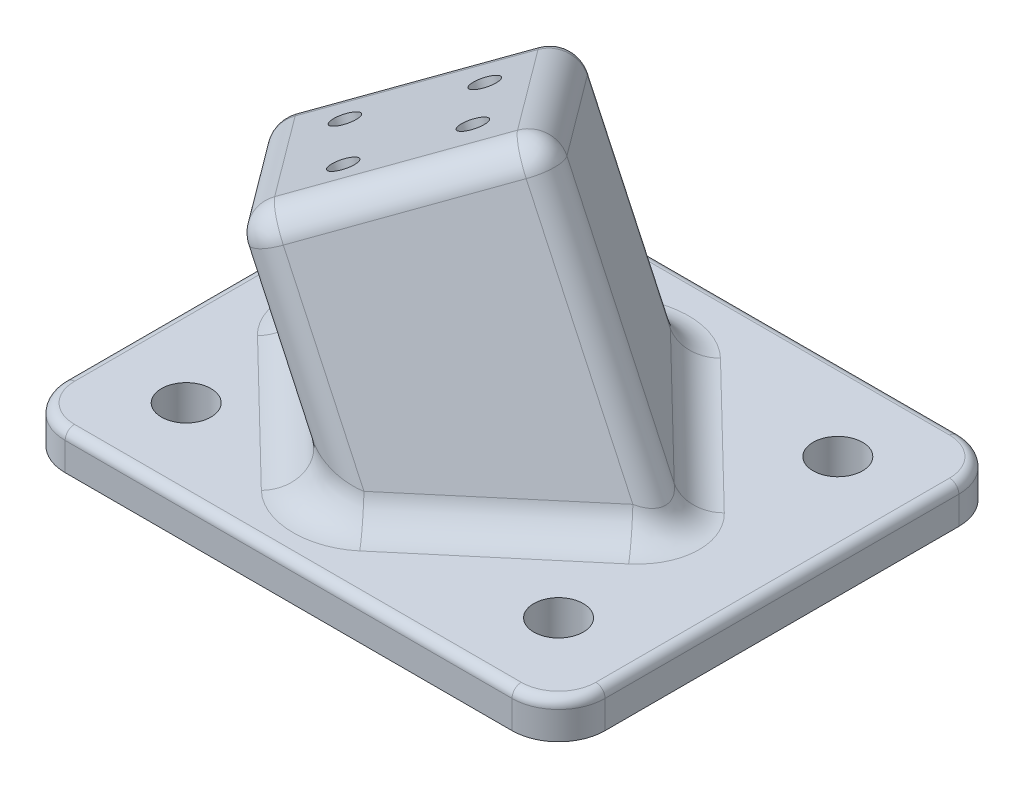
SolidWorks part; units mm, degrees
ref_plane "Front Plane" through (0, 0, 0) normal (0, 0, 1) x (1, 0, 0)
ref_plane "Top Plane" through (0, 0, 0) normal (0, 1, 0) x (1, 0, 0)
ref_plane "Right Plane" through (0, 0, 0) normal (1, 0, 0) x (0, 0, -1)
sketch "Sketch1" plane through (0, 0, 0) normal (0, 1, 0) x (1, 0, 0)
  line L1 (0, 0) -> (63.5, 0)
  line L2 (0, 0) -> (0, -50.8)
  line L3 (0, -50.8) -> (63.5, -50.8)
  line L4 (63.5, 0) -> (63.5, -50.8)
  dimension "D1" = 63.5
  dimension "D2" = 50.8
extrude "Boss-Extrude1" add sketch "Sketch1" along normal blind 5.08
sketch "Sketch2" plane through (0, 5.08, 0) normal (0, 1, 0) x (1, 0, 0)
  line L1 (0, 0) -> (0, -50.8) construction
  line L2 (63.5, 0) -> (0, 0) construction
  point P0 (6.35, -6.35)
  point P1 (57.15, -6.35)
  point P2 (57.15, -44.45)
  point P3 (6.35, -44.45)
  dimension "D1" = 50.8
  dimension "D2" = 38.1
  dimension "D3" = 50.8
  dimension "D4" = 38.1
  dimension "D5" = 6.35
  dimension "D6" = 6.35
ref_plane "Plane2" through (11.3415, -24.3219, 0) normal (-0.4226, 0.9063, 0) x (0, 0, -1)
sketch "Sketch5" plane through (0, 0, 0) normal (0, -1, 0) x (1, 0, 0)
  line L0 (0, 0) -> (0, 50.8) construction
  line L1 (0, 50.8) -> (63.5, 50.8)
  line L2 (0, 50.8) -> (0, 0)
  line L3 (0, 0) -> (63.5, 0)
  line L4 (63.5, 50.8) -> (63.5, 0)
  line L5 (63.5, 0) -> (0, 0) construction
  dimension "D1" = 50.8
  dimension "D2" = 63.5
  dimension "D3" = 0
  dimension "D4" = 0
hole_wizard "1/4 Clearance Hole1" positions "3DSketch2" profile "Sketch8" hole size "1/4" standard "ANSI Inch" end condition up to next
sketch3d "3DSketch2"
  point P0 (6.35, 5.08, 6.35)
  point P3 (6.35, 5.08, 44.45)
  point P6 (57.15, 5.08, 44.45)
  point P9 (57.15, 5.08, 6.35)
sketch "Sketch8" plane through (6.35, 5.08, 6.35) normal (1, 0, 0) x (0, 0, 1)
  line L0 (0, 0) -> (0, 5.08)
  line L1 (0, 5.08) -> (3.3782, 5.08)
  line L2 (3.3782, 5.08) -> (3.3782, 0)
  line L5 (3.3782, 0) -> (0, 0)
  line L11 (0, -6.35) -> (0, 107.95) construction
  dimension "Thru Hole Dia." = 6.7564
  dimension "Thru Hole Depth" = 5.08
sketch "Sketch13" plane through (0, 5.08, 0) normal (0, 1, 0) x (1, 0, 0)
  line L0 (0, 0) -> (63.5, 0)
  line L1 (63.5, 0) -> (63.5, -50.8)
  line L2 (63.5, -50.8) -> (0, -50.8)
  line L3 (0, 0) -> (0, -50.8) construction
  line L4 (0, -50.8) -> (63.5, -50.8) construction
  line L5 (0, -50.8) -> (0, 0)
  line L6 (-5.08, 5.08) -> (68.58, 5.08)
  line L7 (68.58, 5.08) -> (68.58, -55.88)
  line L8 (68.58, -55.88) -> (-5.08, -55.88)
  line L9 (-5.08, -55.88) -> (-5.08, 5.08)
  dimension "D1" = 73.66
  dimension "D2" = 60.96
  dimension "D3" = 5.08
  dimension "D4" = 5.08
extrude "Boss-Extrude3" add sketch "Sketch13" against normal blind 5.08
fillet "Fillet4" radius 1.27 4 edges at (68.58, 5.08, 25.4) (31.75, 5.08, -5.08) (31.75, 5.08, 55.88) (-5.08, 5.08, 25.4)
sketch "Sketch14" plane through (11.3415, -24.3219, 0) normal (-0.4226, 0.9063, 0) x (0, 0, -1)
  line L0 (-25.4, -8.3855) -> (-48.992, -30.3854)
  line L1 (-48.992, -30.3854) -> (-26.9921, -53.9775)
  line L2 (-26.9921, -53.9775) -> (-3.4001, -31.9775)
  line L3 (-3.4001, -31.9775) -> (-25.4, -8.3855)
  line L4 (5.08, 4.604) -> (-55.88, 4.604) construction
  line L6 (-55.88, -63.7648) -> (-55.88, 2.9939) construction
  point P6 (-25.4, 4.604)
  point P11 (-55.88, -30.3854)
  dimension "D1" = 90
  dimension "D2" = 90
  dimension "D3" = 32.258
  dimension "D4" = 32.258
extrude "Boss-Extrude4" add sketch "Sketch14" along normal blind 50.8
sketch "Sketch16" plane through (0, 0, 0) normal (0, -1, 0) x (1, 0, 0)
  line L1 (0, 50.8) -> (63.5, 50.8)
  line L2 (0, 50.8) -> (0, 0)
  line L3 (0, 0) -> (63.5, 0)
  line L4 (63.5, 50.8) -> (63.5, 0)
sketch "Sketch17" plane through (11.3415, -24.3219, 0) normal (0.4226, -0.9063, 0) x (0.9063, 0.4226, 0)
  line L0 (11.9755, 25.5254) -> (31.8522, 6.99)
  line L1 (31.8522, 6.99) -> (50.3875, 26.8667)
  line L2 (50.3875, 26.8667) -> (30.5108, 45.4021)
  line L3 (30.5108, 45.4021) -> (11.9755, 25.5254)
  line L5 (31.9775, 3.4001) -> (8.3855, 25.4) construction
  line L6 (8.3855, 25.4) -> (30.3854, 48.992) construction
  line L7 (53.9775, 26.9921) -> (30.3854, 48.992) construction
  line L8 (31.9775, 3.4001) -> (53.9775, 26.9921) construction
  dimension "D1" = 2.54
  dimension "D2" = 2.54
  dimension "D3" = 2.54
  dimension "D4" = 2.54
extrude "Cut-Extrude2" cut sketch "Sketch17" against normal blind 45.72
extrude "Cut-Extrude1" cut sketch "Sketch5" along normal up to next contours L2 L3 L4 L1
sketch "Sketch18" plane through (-10.1275, 21.7185, 0) normal (-0.4226, 0.9063, 0) x (0.9063, 0.4226, 0)
  line L0 (31.9775, -3.4001) -> (53.9775, -26.9921) construction
  line L1 (53.9775, -26.9921) -> (30.3854, -48.992) construction
  point P0 (40.8281, -25.8748)
  point P1 (31.1815, -26.196)
  point P2 (21.5295, -25.8288)
  point P3 (32.3273, -16.544)
  point P4 (32.3273, -35.848)
  dimension "D1" = 16.129
  dimension "D2" = 16.129
  dimension "D3" = 9.652
  dimension "D4" = 9.652
  dimension "D5" = 9.652
  dimension "D6" = 9.652
hole_wizard "M3 Clearance Hole1" positions "3DSketch3" profile "Sketch19" hole size "M3" standard "ANSI Metric" end condition through all
sketch3d "3DSketch3"
  point P0 (19.1709, 35.3806, 16.544)
  point P3 (26.8754, 38.9732, 25.8748)
  point P6 (19.1709, 35.3806, 35.848)
  point P9 (9.3848, 30.8173, 25.8288)
sketch "Sketch19" plane through (19.1709, 35.3806, 16.544) normal (0, 0, 1) x (-0.9063, -0.4226, 0)
  line L0 (0, 0) -> (0, 52.9469)
  line L1 (0, 52.9469) -> (1.7, 52.9469)
  line L2 (1.7, 52.9469) -> (1.7, 0)
  line L5 (1.7, 0) -> (0, 0)
  line L11 (0, -6.35) -> (0, 107.95) construction
  dimension "Thru Hole Dia." = 3.4
  dimension "Thru Hole Depth" = 52.9469
fillet "Fillet5" radius 3.81 8 edges at (28.8233, 39.8816, 15.1961) (25.8842, 20.1564, 3.4001) (8.1632, 30.2476, 14.4) (2.178, 15.1712, 25.4) (7.4417, 29.9112, 37.196) (24.2844, 19.82, 48.992) (28.1019, 39.5452, 37.9921) (47.9907, 24.8052, 26.9921)
fillet "Fillet6" radius 6.35 8 edges at (68.208, 4.708, -4.708) (-4.708, 4.708, -4.708) (-4.708, 4.708, 55.508) (68.208, 4.708, 55.508) (68.58, 1.905, 55.88) (-5.08, 1.905, 55.88) (-5.08, 1.905, -5.08) (68.58, 1.905, -5.08)
fillet "Fillet7" radius 5.08 8 edges at (45.0516, 5.08, 15.1961) (19.899, 5.08, 14.4) (19.0207, 5.08, 37.196) (44.1732, 5.08, 37.9921) (8.6238, 5.08, 25.4551) (31.2186, 5.08, 47.4148) (32.8537, 5.08, 4.9773) (55.4484, 5.08, 26.937)
fillet "Fillet8" radius 1.27 4 edges at (11.2722, 26.0922, 35.4637) (28.6788, 34.209, 36.1344) (29.2866, 34.4925, 16.9284) (11.8801, 26.3757, 16.2577)
